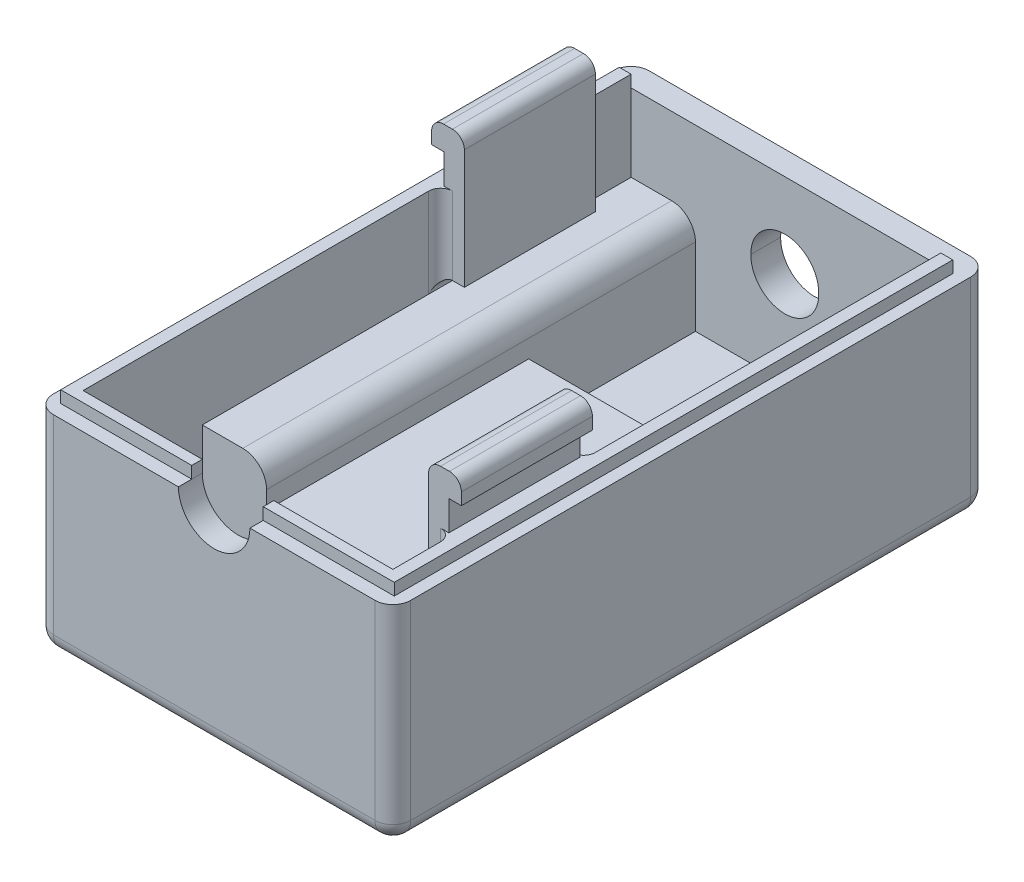
SolidWorks part; units mm, degrees
ref_plane "Front Plane" through (0, 0, 0) normal (0, 0, 1) x (1, 0, 0)
ref_plane "Top Plane" through (0, 0, 0) normal (0, 1, 0) x (1, 0, 0)
ref_plane "Right Plane" through (0, 0, 0) normal (1, 0, 0) x (0, 0, -1)
sketch "Sketch1" plane through (0, 0, 0) normal (0, 1, 0) x (1, 0, 0)
  line L1 (-15, 20) -> (15, 20)
  line L2 (-15, 20) -> (-15, -20)
  line L4 (15, 20) -> (15, -20)
  line L5 (-15, 20) -> (15, -20) construction
  line L6 (-15, -20) -> (15, 20) construction
  line L8 (-15, -20) -> (-15, -30)
  line L9 (-15, -30) -> (15, -30)
  line L10 (15, -20) -> (15, -30)
  point P0 (0, 0)
  dimension "D1" = 40
  dimension "D2" = 30
  dimension "D3" = 10
extrude "Boss-Extrude1" add sketch "Sketch1" along normal blind 17.5
sketch "Sketch2" plane through (0, 17.5, 0) normal (0, 1, 0) x (1, 0, 0)
  line L0 (15, -30) -> (15, 20) construction
  line L1 (-13, 18) -> (13, 18)
  line L2 (-13, 18) -> (-13, -18)
  line L4 (13, 18) -> (13, -18)
  line L5 (-13, 18) -> (13, -18) construction
  line L6 (-13, -18) -> (13, 18) construction
  line L8 (-15, -30) -> (15, -30) construction
  line L10 (-13, -18) -> (-13, -28)
  line L11 (-13, -28) -> (13, -28)
  line L12 (13, -18) -> (13, -28)
  point P0 (0, 0)
  dimension "D1" = 2
  dimension "D3" = 2
extrude "Cut-Extrude1" cut sketch "Sketch2" against normal blind 14
sketch "Sketch3" plane through (0, 0, -18) normal (0, 0, 1) x (1, 0, 0)
  line L43 (1.569, 6.4463) -> (3.9294, 8.8066)
  line L44 (-0.1, 10.3757) -> (-0.1, 10.4757)
  line L45 (3.9294, 8.8066) -> (3.9294, 12.1447)
  line L46 (3.9294, 12.1447) -> (1.569, 14.5051)
  line L47 (1.569, 14.5051) -> (-1.769, 14.5051)
  line L48 (-1.769, 14.5051) -> (-4.1294, 12.1447)
  line L49 (-4.1294, 12.1447) -> (-4.1294, 8.8066)
  line L50 (-4.1294, 8.8066) -> (-1.769, 6.4463)
  line L51 (-1.769, 6.4463) -> (1.569, 6.4463)
  arc A3 (2.7496, 10.4257) -> (-2.9496, 10.4257) centre (-0.1, 10.4757) ccw
  arc A4 (-2.9496, 10.4257) -> (2.7496, 10.4257) centre (-0.1, 10.3757) ccw
  dimension "D3" = 5.7
  dimension "D4" = 5.7
extrude "Cut-Extrude2" cut sketch "Sketch3" against normal through all contours A3 A4 region at (-0.1, 7.607, -18)
sketch "Sketch4" plane through (0, 3.5, 0) normal (0, 1, 0) x (1, 0, 0)
  line L0 (13, -28) -> (13, 18) construction
  line L1 (-13, 18) -> (13, 18)
  line L2 (-13, 18) -> (-13, 10)
  line L3 (-13, 10) -> (13, 10)
  line L4 (13, 18) -> (13, 10)
  dimension "D1" = 8
extrude "Cut-Extrude3" cut sketch "Sketch4" against normal blind 1
sketch "Sketch6" plane through (0, 3.5, 0) normal (0, 1, 0) x (1, 0, 0)
  line L0 (-13, -18) -> (13, -18) construction
  line L1 (-13, 18) -> (-7.6, 18)
  line L2 (-13, 18) -> (-13, -18)
  line L3 (-13, -18) -> (-7.6, -18)
  line L4 (-7.6, 18) -> (-7.6, -18)
  line L6 (13, -18) -> (7.6, -18)
  line L7 (13, 18) -> (13, -18)
  line L8 (7.6, 18) -> (7.6, -18)
  line L9 (13, 18) -> (7.6, 18)
  dimension "D1" = 5.4
extrude "Boss-Extrude3" add sketch "Sketch6" along normal blind 7.5 and the other way blind 1
fillet "Fillet2" radius 2 2 edges at (-7.6, 11, 0) (7.6, 11, 0)
fillet "Fillet5" radius 1.5 8 edges at (-15, 0, 5) (-15, 8.75, -20) (0, 0, -20) (15, 0, 5) (15, 8.75, -20) (-15, 8.75, 30) (15, 8.75, 30) (0, 0, 30)
sketch "Sketch13" plane through (0, 3.5, 0) normal (0, 1, 0) x (1, 0, 0)
  line L1 (-7.6, 10) -> (7.6, 10)
  line L2 (-7.6, 10) -> (-7.6, -18)
  line L3 (-7.6, -18) -> (7.6, -18)
  line L4 (7.6, 10) -> (7.6, -18)
extrude "Boss-Extrude7" add sketch "Sketch13" along normal blind 4
sketch "Sketch15" plane through (0, 7.5, 0) normal (0, 1, 0) x (1, 0, 0)
  circle A0 centre (0, -8.82) radius 1
  dimension "D2" = 2
extrude "Cut-Extrude8" cut sketch "Sketch15" against normal blind 6
chamfer "Chamfer5" distance 6 angle 45 1 edges at (0, 7.5, -10)
sketch "Sketch16" plane through (-13, 0, 0) normal (1, 0, 0) x (0, 0, -1)
  line L0 (18, 17.5) -> (-28, 17.5) construction
  line L2 (2, 14.5) -> (2, 17.5)
  line L3 (13, 14.5) -> (13, 12)
  line L5 (13, 12) -> (2, 12)
  line L6 (13, 12) -> (13, 14.5)
  line L8 (2, 12) -> (2, 14.5)
  line L9 (13, 14.5) -> (13, 17.5)
  line L10 (13, 17.5) -> (13, 14.5)
  line L12 (2, 17.5) -> (2, 23)
  line L13 (2, 23) -> (13, 23)
  line L14 (13, 17.5) -> (13, 23)
  line M12 (18, 17.5) -> (-28, 17.5)
  dimension "D1" = 5.5
  dimension "D2" = 11
sketch "Sketch17" plane through (13, 0, 0) normal (-1, 0, 0) x (0, 0, 1)
  line L0 (28, 17.5) -> (23, 17.5)
  line L3 (12, 14.5) -> (12, 12)
  line L4 (12, 12) -> (23, 12)
  line L5 (23, 12) -> (23, 14.5)
  line L6 (12, 14.5) -> (12, 23)
  line L7 (12, 23) -> (23, 23)
  line L8 (23, 14.5) -> (23, 23)
  line L9 (28, 17.5) -> (-18, 17.5) construction
  line M9 (28, 17.5) -> (-18, 17.5)
  dimension "D1" = 8.5
  dimension "D2" = 5
  dimension "D4" = 2.5
  dimension "D5" = 11
extrude "Boss-Extrude8" add sketch "Sketch16" along normal blind 2 contours L3 L9 L2 L8 L5 M12 | L14 L13 L12 M12 region at (-13, 14.75, -7.5) region at (-13, 20.25, -7.5)
extrude "Boss-Extrude9" add sketch "Sketch17" along normal blind 2 contours L8 L7 L6 M9 | L5 L8 L6 L3 L4 M9 region at (13, 14.75, 17.5) region at (13, 20.25, 17.5)
extrude "Boss-Extrude14" add sketch "Sketch3<4>" against normal blind 0.5 from offset 2 contours L50 L51 L43 L45 L46 L47 L48 L49 A4 A3 region at (-0.1, 6.5602, -18) offset against normal yes
sketch "Sketch3<4>" plane through (0, 0, -18) normal (0, 0, 1) x (1, 0, 0) same geometry as "Sketch3"
chamfer "Chamfer6" distance 0.5 angle 45 8 edges at (2.7492, 13.3249, -20.5) (3.9294, 10.4757, -20.5) (2.7492, 7.6265, -20.5) (-0.1, 6.4463, -20.5) (-2.9492, 7.6265, -20.5) (-4.1294, 10.4757, -20.5) (-2.9492, 13.3249, -20.5) (-0.1, 14.5051, -20.5)
sketch "Sketch23" plane through (0, 0, 0) normal (0, -1, 0) x (1, 0, 0)
  line L2 (-12, 17) -> (-12, -17)
  line L3 (-12, -17) -> (12, -17)
  line L4 (12, 17) -> (12, -17)
  line L5 (-12, 17) -> (12, -17) construction
  line L6 (-12, -17) -> (12, 17) construction
  line L8 (-12, 17) -> (-12, 27)
  line L9 (-12, 27) -> (12, 27)
  line L10 (12, 17) -> (12, 27)
  point P0 (0, 0)
  dimension "D1" = 24
  dimension "D2" = 34
  dimension "D3" = 10
extrude "Boss-Extrude15" add sketch "Sketch23" along normal blind 0.5
chamfer "Chamfer7" distance 0.5 angle 45 4 edges at (12, -0.5, 5) (-12, -0.5, 5) (0, -0.5, -17) (0, -0.5, 27)
sketch "Sketch24" plane through (0, 0, 30) normal (0, 0, 1) x (1, 0, 0)
  line L0 (-13.5, 17.5) -> (13.5, 17.5) construction
  line L1 (-3, 17.5) -> (3, 17.5)
  arc A0 (-3, 17.5) -> (3, 17.5) centre (0, 17.5) ccw
  dimension "D1" = 6
extrude "Cut-Extrude9" cut sketch "Sketch24" against normal up to next
sketch "Sketch26" plane through (0, 17.5, 0) normal (0, 1, 0) x (1, 0, 0)
  line L0 (13, -28) -> (13, -23) construction
  line L2 (-13, 18) -> (-13, -28)
  line L3 (-13, -28) -> (-3, -28)
  line L4 (13, 18) -> (13, -28)
  line L5 (14, -28.8842) -> (3, -28.8842)
  line L7 (-14, 18) -> (-14, -19.1158)
  line L9 (14, 18) -> (14, -28.8842)
  line L10 (-13.1828, 18) -> (-13, 17.7504) construction
  line L11 (-14, -28.8842) -> (-14, -19.1158)
  line L12 (13, 17.7504) -> (13.1828, 18) construction
  line L13 (-13, 18) -> (-14, 18)
  line L14 (-14, 18) -> (-13, 18)
  line L16 (13, 18) -> (14, 18)
  line L17 (-3, -28) -> (-3, -28.8842)
  line L19 (3, -28) -> (3, -30) construction
  line L20 (3, -28.8842) -> (3, -28)
  line L21 (3, -28) -> (13, -28)
  line L22 (-3, -28.8842) -> (-14, -28.8842)
  point P7 (0, 0)
  line M6 (-3, -30) -> (-3, -28)
  line M7 (-3, -28) -> (-13, -28)
  line M8 (-13, -28) -> (-13, 2)
  line M11 (-13, 2) -> (-13, 13)
  line M14 (-13, 13) -> (-13, 18)
extrude "Boss-Extrude16" add sketch "Sketch26" along normal blind 1 contours L22 L2 L13 L7 L11 M6 M7 M8 M11 M14 | L21 L4 L16 L9 L5 L20 region at (-13.4816, 17.5, -15.5)
fillet "Fillet7" radius 1 7 edges at (-13, 15.25, -13) (-13, 12, -7.5) (-13, 15.25, -2) (13, 12, 17.5) (13, 15.25, 12) (13, 15.25, 23) (0, 3.5, 18)
sketch "Sketch27" plane through (-13, 0, 0) normal (-1, 0, 0) x (0, 0, 1)
  line L0 (-2, 18.5) -> (-2, 23) construction
  line L1 (-13, 23) -> (-2, 23)
  line L2 (-13, 23) -> (-13, 21)
  line L3 (-13, 21) -> (-2, 21)
  line L4 (-2, 23) -> (-2, 21)
  line L5 (-18, 18.5) -> (28.8842, 18.5) construction
  line L6 (-13, 21) -> (-2, 21)
  line L7 (-13, 21) -> (-13, 18.5)
  line L8 (-13, 18.5) -> (-2, 18.5)
  line L9 (-2, 21) -> (-2, 18.5)
  line M2 (-13, 23) -> (-13, 18.5)
  line M3 (-13, 18.5) -> (-2, 18.5)
  line M4 (-2, 18.5) -> (-2, 23)
  line M5 (-2, 23) -> (-13, 23)
  dimension "D1" = 2
extrude "Boss-Extrude17" add sketch "Sketch27" along normal blind 0.75 contours L3 M2 M4 M5 region at (-13, 22, -7.5)
extrude "Cut-Extrude10" cut sketch "Sketch27<3>" against normal blind 0.3 contours L3 M2 M3 M4 region at (-13, 19.75, -7.5)
sketch "Sketch27<3>" plane through (-13, 0, 0) normal (-1, 0, 0) x (0, 0, 1) same geometry as "Sketch27"
sketch "Sketch29" plane through (13, 0, 0) normal (1, 0, 0) x (0, 0, -1)
  line L1 (-23, 23) -> (-12, 23)
  line L2 (-23, 23) -> (-23, 21)
  line L3 (-23, 21) -> (-12, 21)
  line L4 (-12, 23) -> (-12, 21)
  line L5 (-23, 21) -> (-12, 21)
  line L6 (-23, 21) -> (-23, 18.5)
  line L7 (-23, 18.5) -> (-12, 18.5)
  line L8 (-12, 21) -> (-12, 18.5)
  line M2 (-23, 18.5) -> (-12, 18.5)
  line M3 (-12, 18.5) -> (-12, 23)
  line M4 (-12, 23) -> (-23, 23)
  line M5 (-23, 23) -> (-23, 18.5)
  dimension "D1" = 2
extrude "Boss-Extrude18" add sketch "Sketch29" along normal blind 0.75 contours L3 M5 M3 M4 region at (13, 22, 17.5)
extrude "Cut-Extrude11" cut sketch "Sketch29<4>" against normal blind 0.3 contours L3 M5 M2 M3 region at (13, 19.75, 17.5)
sketch "Sketch29<4>" plane through (13, 0, 0) normal (1, 0, 0) x (0, 0, -1) same geometry as "Sketch29"
fillet "Fillet8" radius 1 4 edges at (11, 23, 17.5) (13.75, 23, 17.5) (-11, 23, -7.5) (-13.75, 23, -7.5)
